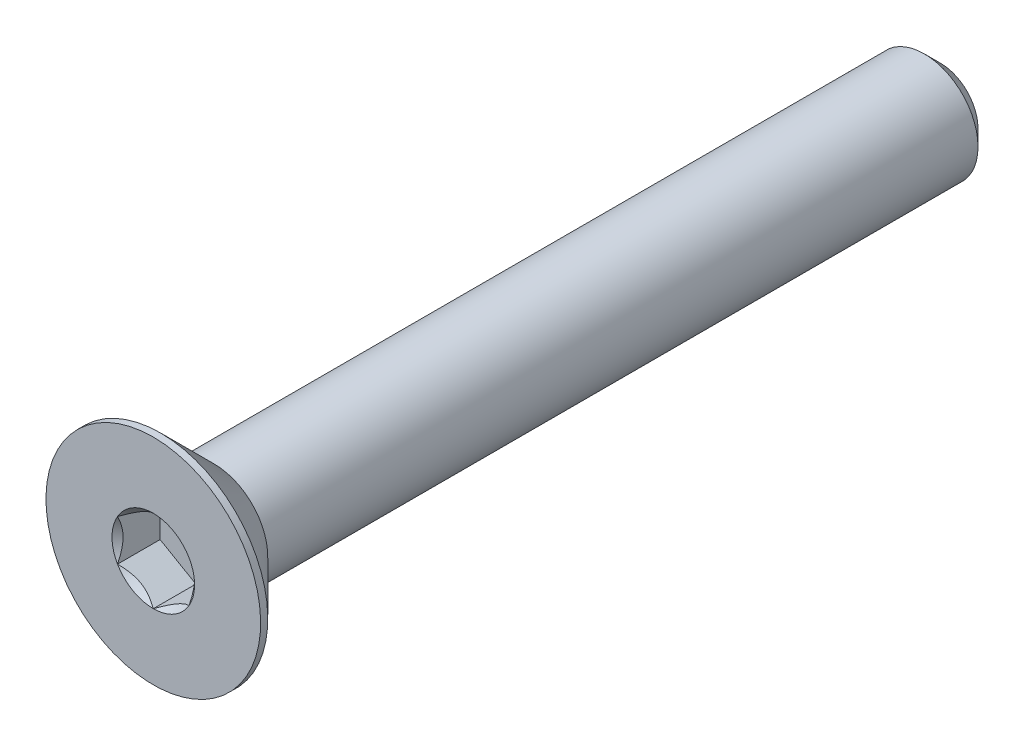
SolidWorks part; units mm, degrees
material "Alloy Steel"
ref_plane "Front" through (0, 0, 0) normal (0, 0, 1) x (1, 0, 0)
ref_plane "Top" through (0, 0, 0) normal (0, 1, 0) x (1, 0, 0)
ref_plane "Right" through (0, 0, 0) normal (1, 0, 0) x (0, 0, -1)
sketch "Sketch1" plane through (0, 0, 0) normal (1, 0, 0) x (0, 0, -1)
  line L0 (-11, 3) -> (-10.8, 3) construction
  line L1 (-10.8, 3) -> (-9.3, 1.5) construction
  line L2 (-11, 1.5) -> (11, 1.5) construction
  line L3 (11, 1.5) -> (11, 0) construction
  line L4 (11, 0) -> (-11, 0) construction
  line L5 (-11, 0) -> (-11, 3) construction
  line L6 (-11, 3) -> (-11, -3) construction
  line L7 (11, 1.5) -> (11, -1.5) construction
  line L8 (-11, -3) -> (-10.8, -3) construction
  line L9 (-10.8, -3) -> (-9.3, -1.5) construction
  line L11 (-11, 1.5) -> (-11, 0) construction
  line L12 (-9.3, 1.5) -> (-9.3, 0) construction
  line L13 (10.9688, 1.5541) -> (11.2188, 1.1211) construction
  line L14 (11.2188, 1.1211) -> (11.4688, 1.5541) construction
  line L15 (11.4688, 1.5541) -> (10.9688, 1.5541) construction
  line L16 (11.2188, 1.5541) -> (11.2188, 1.5) construction
  line L17 (11.2188, 1.5) -> (11.2188, 1.1752) construction
  line L18 (11.2188, 1.1752) -> (11.2188, 1.1211) construction
  line L19 (11.2188, 1.5271) -> (11.4531, 1.5271) construction
  line L20 (11.2188, 1.5271) -> (10.9844, 1.5271) construction
  line L21 (11, 1.5) -> (11.4375, 1.5) construction
  line L22 (11.1875, 1.1752) -> (11.25, 1.1752) construction
  line L23 (11, -1.5) -> (-9.3, -1.5) construction
  point P10 (9.75, -1.5)
  point P24 (-9.3, 1.5)
  point P30 (0, 0)
  dimension "Head Diameter" = 6
  dimension "Head Height" = 1.7
  dimension "Length" = 22
  dimension "Countersink Angle" = 90
  dimension "Thread Pitch" = 0.5
  dimension "D2" = 0.0625
  dimension "Minimum Thread Length" = 20.3
  dimension "Thread Size" = 3
  dimension "D1" = 1.25
sketch "Sketch2" plane through (0, 0, 0) normal (0, 0, 1) x (1, 0, 0)
  line L1 (0, 1.1547) -> (-1, 0.5774) construction
  line L2 (-1, 0.5774) -> (-1, -0.5774) construction
  line L3 (-1, -0.5774) -> (0, -1.1547) construction
  line L4 (0, -1.1547) -> (1, -0.5774) construction
  line L5 (1, -0.5774) -> (1, 0.5774) construction
  line L6 (1, 0.5774) -> (0, 1.1547) construction
  circle A0 centre (0, 0) radius 1 construction
  dimension "Drive Size" = 2
sketch "Sketch3" plane through (0, 0, 0) normal (1, 0, 0) x (0, 0, -1)
  line L0 (-11, 1.5) -> (11, 1.5)
  line L1 (11, 1.5) -> (11, 0)
  line L2 (11, 0) -> (-11, 0)
  line L3 (-11, 0) -> (-11, 1.5)
revolve "Revolve1" add sketch "Sketch3" angle 360 about L4
chamfer "Chamfer1" distance 0.45 angle 45 1 edges at (0, 1.5, -11)
sketch "Sketch6" plane through (0, 0, 0) normal (1, 0, 0) x (0, 0, -1)
  line L0 (-11, 3) -> (-10.8, 3)
  line L1 (-10.8, 3) -> (-9.3, 1.5)
  line L2 (-9.3, 1.5) -> (-9.3, 0)
  line L3 (-9.3, 0) -> (-11, 0)
  line L4 (-11, 0) -> (-11, 3)
revolve "Revolve2" add sketch "Sketch6" angle 360 about L4
sketch "Sketch8" plane through (0, 0, 11) normal (0, 0, 1) x (1, 0, 0)
  line L0 (0, 1.1547) -> (-1, 0.5774) construction
  line L1 (1, 0.5774) -> (0, 1.1547) construction
  line L2 (1, -0.5774) -> (1, 0.5774) construction
  line L3 (0, -1.1547) -> (1, -0.5774) construction
  line L4 (-1, 0.5774) -> (-1, -0.5774) construction
  line L5 (-1, -0.5774) -> (0, -1.1547) construction
  line L6 (0, 1.1547) -> (-1, 0.5774)
  line L7 (1, 0.5774) -> (0, 1.1547)
  line L8 (1, -0.5774) -> (1, 0.5774)
  line L9 (0, -1.1547) -> (1, -0.5774)
  line L10 (-1, 0.5774) -> (-1, -0.5774)
  line L11 (-1, -0.5774) -> (0, -1.1547)
extrude "Cut-Extrude1" cut sketch "Sketch8" against normal blind 1.19
sketch "Sketch9" plane through (0, 0, 11) normal (0, 0, 1) x (1, 0, 0)
  circle A0 centre (0, 0) radius 1.1547
extrude "Cut-Extrude2" cut sketch "Sketch9" against normal up to next (1.19 mm away) draft 45
ref_plane "Plane1" [suppressed] through (0, 0, 9.3) normal (0, 0, 1) x (1, 0, 0)
split "Split1" [suppressed] bodies to split 124
sketch "Sketch4" [suppressed] plane through (0, 0, -11) normal (0, 0, -1) x (-1, 0, 0)
  circle A0 centre (0, 0) radius 1.5 construction
  circle A1 centre (0, 0) radius 1.5
curve "Helix/Spiral1" [suppressed] pitch 0.5 height 20.8 turns 41.6
sketch "Sketch10" [suppressed] plane through (0, 0, 0) normal (1, 0, 0) x (0, 0, -1)
  line L0 (10.9844, 1.5271) -> (11.4531, 1.5271)
  line L1 (11.4531, 1.5271) -> (11.25, 1.1752)
  line L2 (11.25, 1.1752) -> (11.1875, 1.1752)
  line L3 (11.1875, 1.1752) -> (10.9844, 1.5271)
sweep "Cut-Sweep1" [suppressed] cut profiles "Sketch10" path "Helix/Spiral1"
equation "\"D2@Sketch1\" = \"Thread Pitch@Sketch1\" / 8"
equation "\"D4@Helix/Spiral1\"=\"Thread Pitch@Sketch1\""
equation "\"D3@Helix/Spiral1\"=\"Minimum Thread Length@Sketch1\"+\"Thread Pitch@Sketch1\""
equation "\"D1@Chamfer1\"=\"Thread Size@Sketch1\"*.15"
equation "\"D1@Cut-Extrude1\"=\"Head Height@Sketch1\"*.7"
equation "\"D1@Sketch1\"=\"Thread Pitch@Sketch1\"*2.5"
